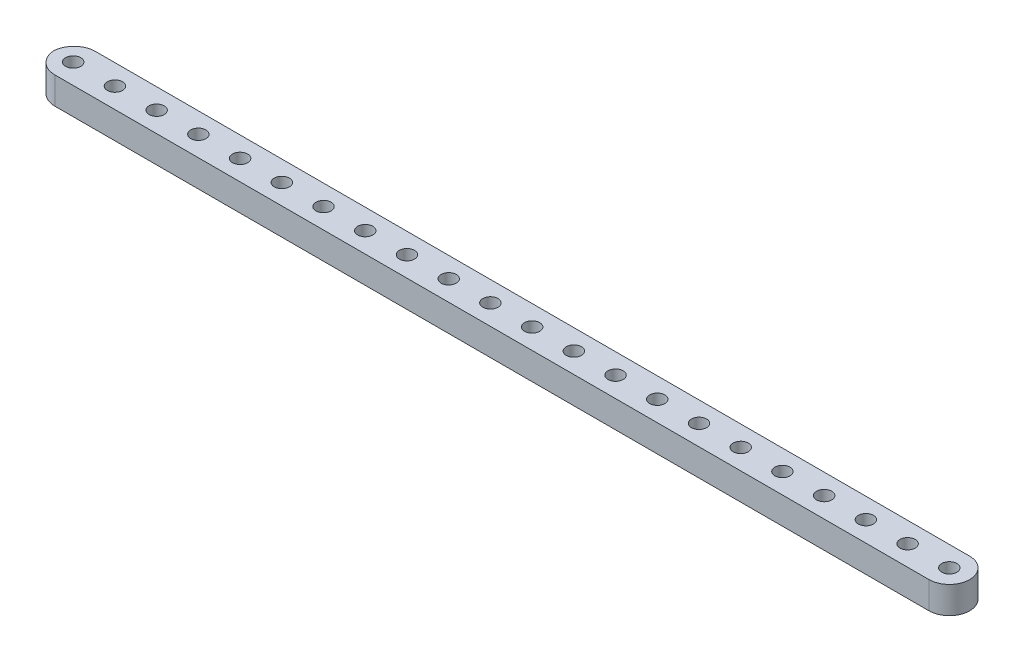
SolidWorks part; units mm, degrees
ref_plane "Front Plane" through (0, 0, 0) normal (0, 0, 1) x (1, 0, 0)
ref_plane "Top Plane" through (0, 0, 0) normal (0, 1, 0) x (1, 0, 0)
ref_plane "Right Plane" through (0, 0, 0) normal (1, 0, 0) x (0, 0, -1)
ref_plane "Plane1" through (0, 6.35, 0) normal (0, 1, 0) x (1, 0, 0)
sketch "Sketch1" plane through (0, 6.35, 0) normal (0, 1, 0) x (1, 0, 0)
  line L0 (156.464, 4.7625) -> (-156.464, 4.7625)
  line L1 (-156.464, -4.7625) -> (156.464, -4.7625)
  arc A0 (156.464, -4.7625) -> (156.464, 4.7625) centre (156.464, 0) ccw
  arc A1 (-156.464, 4.7625) -> (-156.464, -4.7625) centre (-156.464, 0) ccw
  circle A2 centre (156.464, 0) radius 1.778
  circle A3 centre (146.685, 0) radius 1.778
  circle A4 centre (136.906, 0) radius 1.778
  circle A5 centre (127.127, 0) radius 1.778
  circle A6 centre (117.348, 0) radius 1.778
  circle A7 centre (107.569, 0) radius 1.778
  circle A8 centre (97.79, 0) radius 1.778
  circle A9 centre (88.011, 0) radius 1.778
  circle A10 centre (78.232, 0) radius 1.778
  circle A11 centre (68.453, 0) radius 1.778
  circle A12 centre (58.674, 0) radius 1.778
  circle A13 centre (48.895, 0) radius 1.778
  circle A14 centre (39.116, 0) radius 1.778
  circle A15 centre (29.337, 0) radius 1.778
  circle A16 centre (19.558, 0) radius 1.778
  circle A17 centre (9.779, 0) radius 1.778
  circle A18 centre (0, 0) radius 1.778
  circle A19 centre (-9.779, 0) radius 1.778
  circle A20 centre (-19.558, 0) radius 1.778
  circle A21 centre (-29.337, 0) radius 1.778
  circle A22 centre (-39.116, 0) radius 1.778
  circle A23 centre (-48.895, 0) radius 1.778
  circle A24 centre (-58.674, 0) radius 1.778
  circle A25 centre (-68.453, 0) radius 1.778
  circle A26 centre (-78.232, 0) radius 1.778
  circle A27 centre (-88.011, 0) radius 1.778
  circle A28 centre (-97.79, 0) radius 1.778
  circle A29 centre (-107.569, 0) radius 1.778
  circle A30 centre (-117.348, 0) radius 1.778
  circle A31 centre (-127.127, 0) radius 1.778
  circle A32 centre (-136.906, 0) radius 1.778
  circle A33 centre (-146.685, 0) radius 1.778
  circle A34 centre (-156.464, 0) radius 1.778
extrude "Boss-Extrude1" add sketch "Sketch1" against normal blind 6.35
sketch "Sketch2" plane through (0, 6.35, 0) normal (0, 1, 0) x (1, 0, 0)
  line L1 (-161.4373, -14.8403) -> (-53.4873, -14.8403)
  line L2 (-161.4373, -14.8403) -> (-161.4373, 29.1213)
  line L3 (-161.4373, 29.1213) -> (-53.4873, 29.1213)
  line L4 (-53.4873, -14.8403) -> (-53.4873, 29.1213)
  dimension "D1" = 107.95
extrude "Cut-Extrude1" cut sketch "Sketch2" against normal blind 12.7
fillet "Fillet1" radius 5.08 2 edges at (-53.4873, 3.175, 4.7625) (-53.4873, 3.175, -4.7625)
